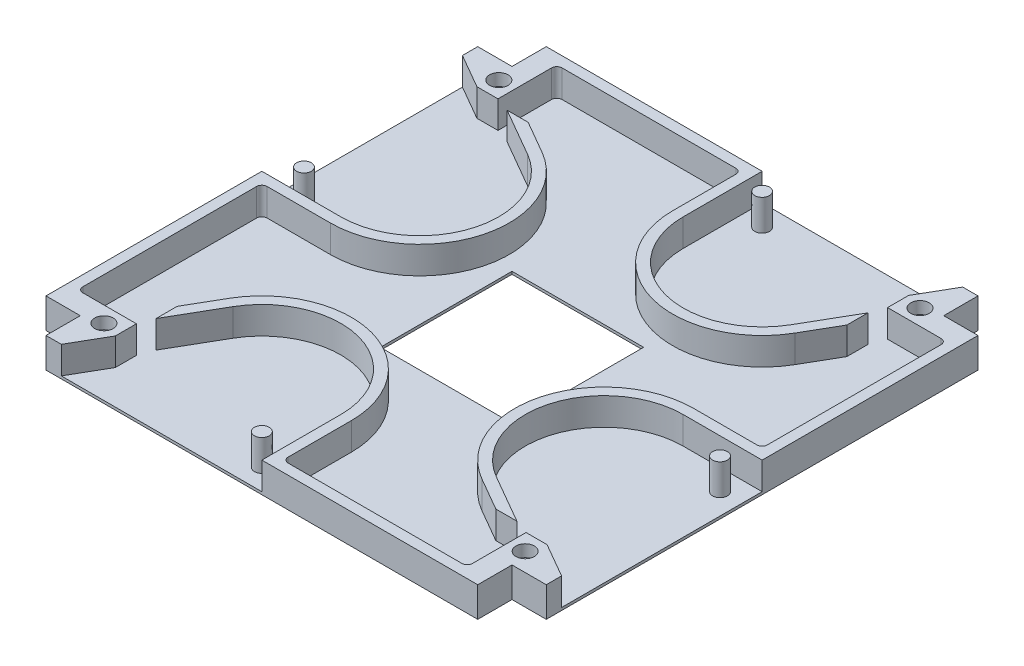
SolidWorks part; units mm, degrees
material "7075-T6 (SN)"
ref_plane "Front Plane" through (0, 0, 0) normal (0, 0, 1) x (1, 0, 0)
ref_plane "Top Plane" through (0, 0, 0) normal (0, 1, 0) x (1, 0, 0)
ref_plane "Right Plane" through (0, 0, 0) normal (1, 0, 0) x (0, 0, -1)
sketch "Sketch1" plane through (0, 0, 0) normal (0, 1, 0) x (1, 0, 0)
  line L0 (0, 0) -> (0, 6.51)
  line L21 (0, 6.51) -> (82, 6.51)
  line L22 (82, 6.51) -> (82, 0)
  line L23 (82, 0) -> (88.51, 0)
  line L24 (88.51, 0) -> (88.51, -82)
  line L25 (88.51, -82) -> (82, -82)
  line L26 (82, -82) -> (82, -88.51)
  line L27 (82, -88.51) -> (0, -88.51)
  line L28 (0, -88.51) -> (0, -82)
  line L29 (0, -82) -> (-6.51, -82)
  line L30 (-6.51, -82) -> (-6.51, 0)
  line L31 (-6.51, 0) -> (0, 0)
  dimension "D1" = 82
  dimension "D2" = 6.51
extrude "Boss-Extrude1" add sketch "Sketch1" along normal blind 0.5
sketch "Sketch2" plane through (0, 0.5, 0) normal (0, 1, 0) x (1, 0, 0)
  line L0 (-6.51, 0) -> (-6.51, -82) construction
  line L1 (0, 6.51) -> (41, 6.51)
  line L2 (0, 6.51) -> (0, 4.51)
  line L3 (0, 4.51) -> (41, 4.51)
  line L4 (41, 6.51) -> (41, 4.51)
  line L5 (88.51, 0) -> (86.51, 0)
  line L6 (88.51, 0) -> (88.51, -41)
  line L7 (88.51, -41) -> (86.51, -41)
  line L8 (86.51, 0) -> (86.51, -41)
  line L9 (82, -88.51) -> (41, -88.51)
  line L10 (82, -88.51) -> (82, -86.51)
  line L11 (82, -86.51) -> (41, -86.51)
  line L12 (41, -88.51) -> (41, -86.51)
  line L13 (-6.51, -82) -> (-4.51, -82)
  line L14 (-6.51, -82) -> (-6.51, -41)
  line L15 (-6.51, -41) -> (-4.51, -41)
  line L16 (-4.51, -82) -> (-4.51, -41)
  line L17 (-6.51, -82) -> (0, -82) construction
  line L18 (41, -8.49) -> (41, 24.5303) construction
  line L19 (56, 6.51) -> (0, 6.51) construction
  line L20 (82, 6.51) -> (0, 6.51) construction
  line L21 (79.094, 6.51) -> (75.3355, 0)
  line L22 (79.094, 6.51) -> (82, 6.51)
  line L23 (82, 6.51) -> (82, 0)
  line L24 (82, 0) -> (86.51, 0)
  line L25 (41, 4.51) -> (41, -8.49)
  line L26 (86.51, -4) -> (75.3355, -4)
  line L27 (39, 4.51) -> (39, -8.49)
  line L28 (72.9929, -8) -> (73.0261, -8)
  line L29 (74.3355, -10.7321) -> (70.7224, -16.99)
  line L31 (75.3355, -4) -> (75.3355, 0)
  line L32 (74.3355, -6.7321) -> (74.3355, -10.7321)
  line L33 (74.3355, -6.7321) -> (68.9904, -15.99)
  circle A0 centre (56, -8.49) radius 15
  circle A1 centre (56, -8.49) radius 17 construction
  arc A2 (70.7224, -16.99) -> (39, -8.49) centre (56, -8.49) cw
  line M24 (88.51, -82) -> (88.51, 0)
  line M25 (88.51, 0) -> (82, 0)
  line M26 (82, 0) -> (82, 6.51)
  line M27 (82, 6.51) -> (0, 6.51)
  line M28 (0, 6.51) -> (0, 0)
  dimension "D3" = 30
  dimension "D6" = 34
  dimension "D1" = 41
  dimension "D2" = 2
  dimension "D7" = 4
  dimension "D8" = 4
  dimension "D5" = 0
  dimension "D9" = 1
  dimension "D4" = 30
  dimension "D10" = 6.6645
  dimension "D11" = 30
  dimension "D12" = 4
extrude "Boss-Extrude2" add sketch "Sketch2" along normal blind 5.2 contours L4 L3 M27 M28 | A2 L28 A0 L25 L3 L27 | L8 L7 M25 M24 | L26 L8 M25 M26 M27 region at (80.332, 0.5, 0.0167) region at (20.5, 0.5, -5.51) region at (40.5365, 0.5, 1.99) region at (87.51, 0.5, 20.5)
sketch "Sketch3" [suppressed] plane through (0, 0.5, 0) normal (0, 1, 0) x (1, 0, 0)
  line L0 (35.5217, -6.4679) -> (39.51, -26.4679)
  line L1 (39.51, -26.4679) -> (39.51, -29.4679)
  line L2 (39.51, -29.4679) -> (79.51, -29.4679)
  line L3 (79.51, -29.4679) -> (79.51, -26.4679)
  line L4 (79.51, -26.4679) -> (83.4983, -6.4679)
  line L6 (35.5217, -6.4679) -> (39.5217, -6.4679)
  line L7 (83.4983, -6.4679) -> (79.4983, -6.4679)
  line L9 (89.51, -41) -> (89.51, 0) construction
  arc A0 (79.4983, -6.4679) -> (39.5217, -6.4679) centre (59.51, -5.7836) cw
  circle A1 centre (58.485, 0) radius 15 construction
  dimension "D3" = 20
  dimension "D7" = 30
  dimension "D1" = 3
  dimension "D2" = 4
  dimension "D4" = 20
  dimension "D5" = 40
  dimension "D6" = 10
extrude "Boss-Extrude3" [suppressed] add sketch "Sketch3" along normal blind 6
ref_plane "Plane1" through (41, 0, 41) normal (0.7071, 0, 0.7071) x (0.7071, 0, -0.7071)
ref_plane "Plane2" through (0, 0, 0) normal (0.7071, 0, -0.7071) x (-0.7071, 0, -0.7071)
ref_axis "Axis1" through (41, -0.325, 41) along (0, 1, 0)
pattern_circular "CirPattern1" count 4 every 90 about axis through (41, -0.325, 41) along (0, 1, 0) of "Boss-Extrude2"
sketch "Sketch4" plane through (0, 0, 0) normal (0, -1, 0) x (1, 0, 0)
  line L0 (78, -6.51) -> (78, -0.51) construction
  line L1 (82, -6.51) -> (0, -6.51) construction
  line L2 (82, 0) -> (82, -6.51) construction
  line L3 (88.51, 78) -> (82.51, 78) construction
  line L4 (88.51, 82) -> (88.51, 0) construction
  line L5 (4, 88.51) -> (4, 82.51) construction
  line L6 (0, 88.51) -> (82, 88.51) construction
  line L7 (-6.51, 4) -> (-0.51, 4) construction
  line L8 (-6.51, 0) -> (-6.51, 82) construction
  line L10 (82, 82) -> (88.51, 82) construction
  line L11 (0, 82) -> (0, 88.51) construction
  line L12 (0, 0) -> (-6.51, 0) construction
  point P7 (78, -0.51)
  dimension "D1" = 6
  dimension "D2" = 4
  dimension "D3" = 4
  dimension "D4" = 4
  dimension "D5" = 4
  dimension "D6" = 6
  dimension "D7" = 6
  dimension "D8" = 6
sketch "Sketch8" plane through (0, 0.5, 0) normal (0, 1, 0) x (1, 0, 0)
  line L0 (2.906, -88.51) -> (41, -88.51) construction
  line L1 (41, -88.51) -> (41, -73.51) construction
  circle A0 centre (37, -84.51) radius 1.4
  dimension "D1" = 2.8
  dimension "D2" = 4
  dimension "D3" = 4
extrude "Boss-Extrude4" add sketch "Sketch8" along normal blind 5.9
pattern_circular "CirPattern2" count 4 every 90 about axis through (41, -0.325, 41) along (0, 1, 0) of "Boss-Extrude4"
fillet "Fillet1" radius 1 8 edges at (-4.51, 3.1, 78) (-4.51, 3.1, 43) (4, 3.1, -4.51) (39, 3.1, -4.51) (86.51, 3.1, 4) (86.51, 3.1, 39) (78, 3.1, 86.51) (43, 3.1, 86.51)
sketch "Sketch11" plane through (0, 0.5, 0) normal (0, 1, 0) x (1, 0, 0)
  line L0 (53.5, -53.5) -> (53.5, -28.5)
  line L1 (53.5, -28.5) -> (28.5, -28.5)
  line L2 (28.5, -28.5) -> (28.5, -53.5)
  line L3 (28.5, -53.5) -> (53.5, -53.5)
  line L5 (79.094, 6.51) -> (41, 6.51) construction
  line L6 (-6.51, -2.906) -> (-6.51, -41) construction
  dimension "D1" = 25
  dimension "D2" = 25
  dimension "D3" = 35.01
  dimension "D4" = 35.01
extrude "Cut-Extrude2" cut sketch "Sketch11" against normal through all
sketch "Sketch12" plane through (0, 0.5, 0) normal (0, 1, 0) x (1, 0, 0)
  line L0 (0, 0) -> (-6.51, 0) construction
  line L2 (82, -88.51) -> (82, -82) construction
  point P0 (40.5, -41.5)
  dimension "D1" = 41.5
  dimension "D2" = 41.5
sketch "Sketch14" plane through (0, 6.4, 0) normal (0, 1, 0) x (1, 0, 0)
  point P0 (37, -84.51)
sketch "Sketch15" plane through (0, 5.7, 0) normal (0, 1, 0) x (1, 0, 0)
  line L0 (82, -82) -> (88.51, -82) construction
  line L2 (78, -85.51) -> (78, -75.3355) construction
  circle A0 centre (81, -78.5) radius 0.9
  circle A1 centre (78.5, -1) radius 0.9
  circle A2 centre (1, -3.5) radius 0.9
  circle A3 centre (3.5, -81) radius 0.9
  point P0 (1, -3.5)
  point P1 (1, -3.5)
  point P2 (3.5, -81)
  point P3 (81, -78.5)
  point P4 (78.5, -1)
  point P5 (3.5, -81)
  dimension "D3" = 1.8
  dimension "D4" = 1.8
  dimension "D5" = 1.8
  dimension "D6" = 1.8
  dimension "D1" = 3.5
  dimension "D2" = 3
extrude "Cut-Extrude3" cut sketch "Sketch15" against normal through all
sketch "Sketch16" plane through (0, 5.7, 0) normal (0, 1, 0) x (1, 0, 0)
  circle A0 centre (78.5, -1) radius 1.75
  circle A1 centre (81, -78.5) radius 1.75
  circle A2 centre (3.5, -81) radius 1.75
  circle A3 centre (1, -3.5) radius 1.75
  dimension "D1" = 3.5
  dimension "D2" = 3.5
  dimension "D3" = 3.5
  dimension "D4" = 3.5
extrude "Cut-Extrude4" cut sketch "Sketch16" against normal blind 2.3
hole_wizard "CBORE for M1.6 SHCS2" positions "3DSketch2" profile "Sketch18" counterbore size "M1.6" standard "ANSI Metric" end condition through all
sketch3d "3DSketch2"
  line L0 (81, 0, 78.5) -> (81, 3.4, 78.5) construction
  line L1 (78.5, 0, 1) -> (78.5, 3.4, 1) construction
  line L2 (1, 0, 3.5) -> (1, 3.4, 3.5) construction
  line L3 (3.5, 0, 81) -> (3.5, 3.4, 81) construction
  point P0 (81, 0, 78.5)
  point P4 (78.5, 0, 1)
  point P8 (1, 0, 3.5)
  point P12 (3.5, 0, 81)
sketch "Sketch18" plane through (81, 0, 78.5) normal (1, 0, 0) x (0, 0, -1)
  line L0 (0, 0) -> (0, 6.4)
  line L1 (0, 6.4) -> (0.9, 6.4)
  line L3 (0.9, 6.4) -> (0.9, 1.6)
  line L4 (0.9, 1.6) -> (1.75, 1.6)
  line L5 (1.75, 1.6) -> (1.75, 0)
  line L7 (1.75, 0) -> (0, 0)
  line L11 (0, -6.35) -> (0, 107.95) construction
  dimension "Thru Hole Dia." = 1.8
  dimension "Thru Hole Depth" = 6.4
  dimension "C'Bore Dia." = 3.5
  dimension "C'Bore Depth" = 1.6
equation "\"D6@Sketch2\"=\"D3@Sketch2\"+4"
equation "\"D3@Sketch4\"=\"D2@Sketch4\""
equation "\"D4@Sketch4\"=\"D3@Sketch4\""
equation "\"D5@Sketch4\"=\"D4@Sketch4\""
equation "\"D6@Sketch4\"=\"D1@Sketch4\""
equation "\"D7@Sketch4\"=\"D6@Sketch4\""
equation "\"D8@Sketch4\"=\"D7@Sketch4\""
